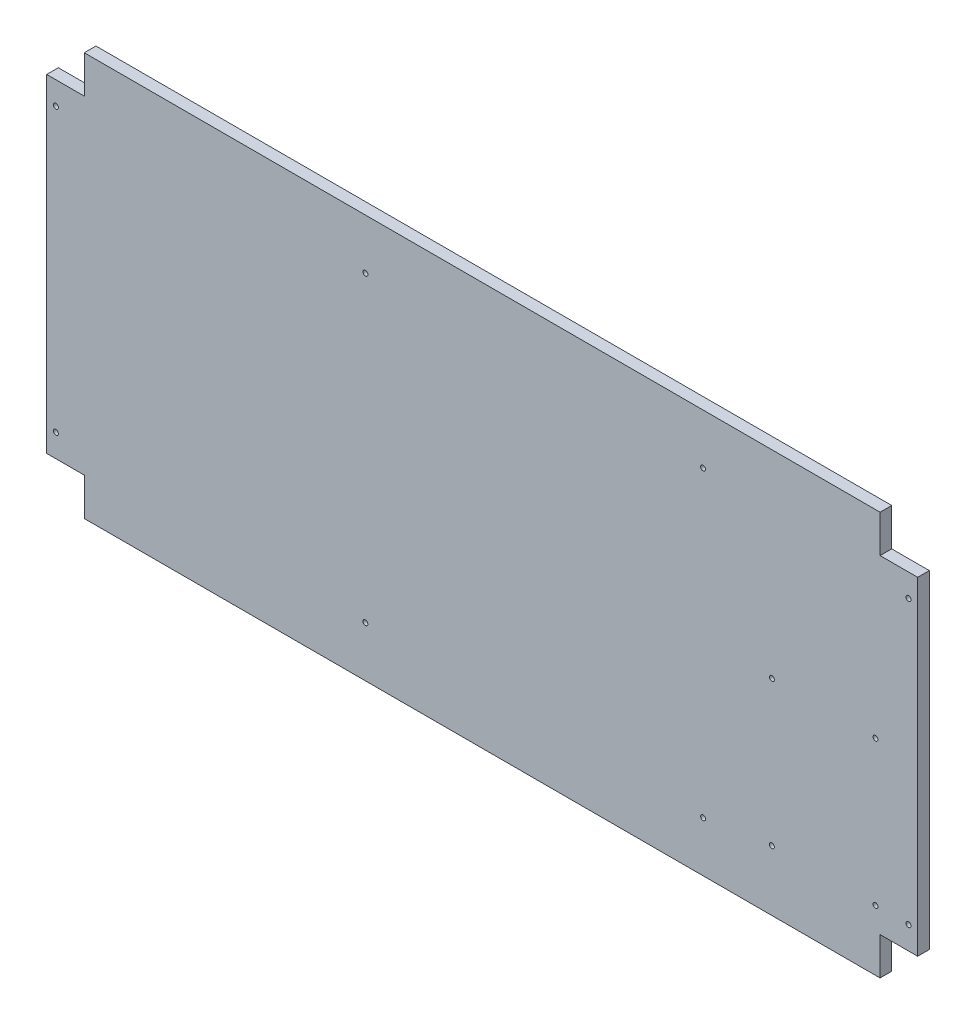
SolidWorks part; units mm, degrees
ref_plane "Front Plane" through (0, 0, 0) normal (0, 0, 1) x (1, 0, 0)
ref_plane "Top Plane" through (0, 0, 0) normal (0, 1, 0) x (1, 0, 0)
ref_plane "Right Plane" through (0, 0, 0) normal (1, 0, 0) x (0, 0, -1)
sketch "Sketch2" plane through (0, 0, 0) normal (0, 0, 1) x (1, 0, 0)
  line L1 (-475, -220) -> (475, -220)
  line L2 (-475, -220) -> (-475, 220)
  line L3 (-475, 220) -> (475, 220)
  line L4 (475, -220) -> (475, 220)
  line L5 (-475, -220) -> (475, 220) construction
  line L6 (-475, 220) -> (475, -220) construction
  point P0 (0, 0)
  dimension "D1" = 950
  dimension "D2" = 440
extrude "Boss-Extrude1" add sketch "Sketch2" along normal blind 12.7
sketch "Sketch3" plane through (0, 0, 12.7) normal (0, 0, 1) x (1, 0, 0)
  line L0 (0, 220) -> (0, -220) construction
  line L1 (-475, 220) -> (-434, 220)
  line L2 (-475, 220) -> (-475, 179)
  line L3 (-475, 179) -> (-434, 179)
  line L4 (-434, 220) -> (-434, 179)
  line L5 (-475, 220) -> (-434, 179) construction
  line L6 (-475, 179) -> (-434, 220) construction
  line L7 (475, 220) -> (-475, 220) construction
  line L8 (-475, -220) -> (475, -220) construction
  line L9 (-475, 0) -> (475, 0) construction
  line L10 (-475, 220) -> (-475, -220) construction
  line L11 (475, -220) -> (475, 220) construction
  line L12 (475, 179) -> (434, 220) construction
  line L13 (475, 220) -> (434, 179) construction
  line L14 (434, 220) -> (434, 179)
  line L15 (475, 179) -> (434, 179)
  line L16 (475, 220) -> (475, 179)
  line L17 (475, 220) -> (434, 220)
  line L18 (475, -220) -> (434, -179) construction
  line L19 (475, -179) -> (434, -220) construction
  line L20 (475, -220) -> (434, -220)
  line L21 (475, -220) -> (475, -179)
  line L22 (434, -220) -> (434, -179)
  line L23 (475, -179) -> (434, -179)
  line L24 (-475, -179) -> (-434, -220) construction
  line L25 (-475, -220) -> (-434, -179) construction
  line L26 (-434, -220) -> (-434, -179)
  line L27 (-475, -179) -> (-434, -179)
  line L28 (-475, -220) -> (-475, -179)
  line L29 (-475, -220) -> (-434, -220)
  point P4 (-454.5, 199.5)
  point P22 (454.5, 199.5)
  point P27 (454.5, -199.5)
  point P32 (-454.5, -199.5)
  dimension "D1" = 41
  dimension "D2" = 41
extrude "Cut-Extrude1" cut sketch "Sketch3" against normal up to next
sketch "Sketch4" plane through (0, 0, 12.7) normal (0, 0, 1) x (1, 0, 0)
  line L0 (-465, 179) -> (-465, -179) construction
  line L1 (-475, 179) -> (-434, 179) construction
  line L2 (-434, -179) -> (-475, -179) construction
  line L3 (0, 220) -> (0, -220) construction
  line L4 (434, 220) -> (-434, 220) construction
  line L5 (-434, -220) -> (434, -220) construction
  line L6 (0, 0) -> (-475, 0) construction
  line L7 (-475, 179) -> (-475, -179) construction
  circle A0 centre (-465, -154) radius 2.75
  circle A1 centre (-465, 154) radius 2.75
  circle A2 centre (465, -154) radius 2.75
  circle A3 centre (465, 154) radius 2.75
  dimension "D1" = 5.5
  dimension "D2" = 25
  dimension "D3" = 10
extrude "Cut-Extrude2" cut sketch "Sketch4" against normal up to next
sketch "Sketch6" plane through (0, 0, 12.7) normal (0, 0, 1) x (1, 0, 0)
  circle A0 centre (-127.35, -165.1) radius 2.665
  circle A1 centre (240.95, -165.1) radius 2.665
  circle A2 centre (240.95, 165.1) radius 2.665
  circle A3 centre (-127.35, 165.1) radius 2.665
  dimension "D1" = 5.33
extrude "Cut-Extrude3" cut sketch "Sketch6" against normal up to next
sketch "Sketch7" plane through (0, 0, 12.7) normal (0, 0, 1) x (1, 0, 0)
  circle A0 centre (429, 4) radius 2.665
  circle A1 centre (429, -154) radius 2.665
  circle A2 centre (316, 4) radius 2.665
  circle A3 centre (316, -154) radius 2.665
  dimension "D1" = 5.33
extrude "Cut-Extrude4" cut sketch "Sketch7" against normal up to next
